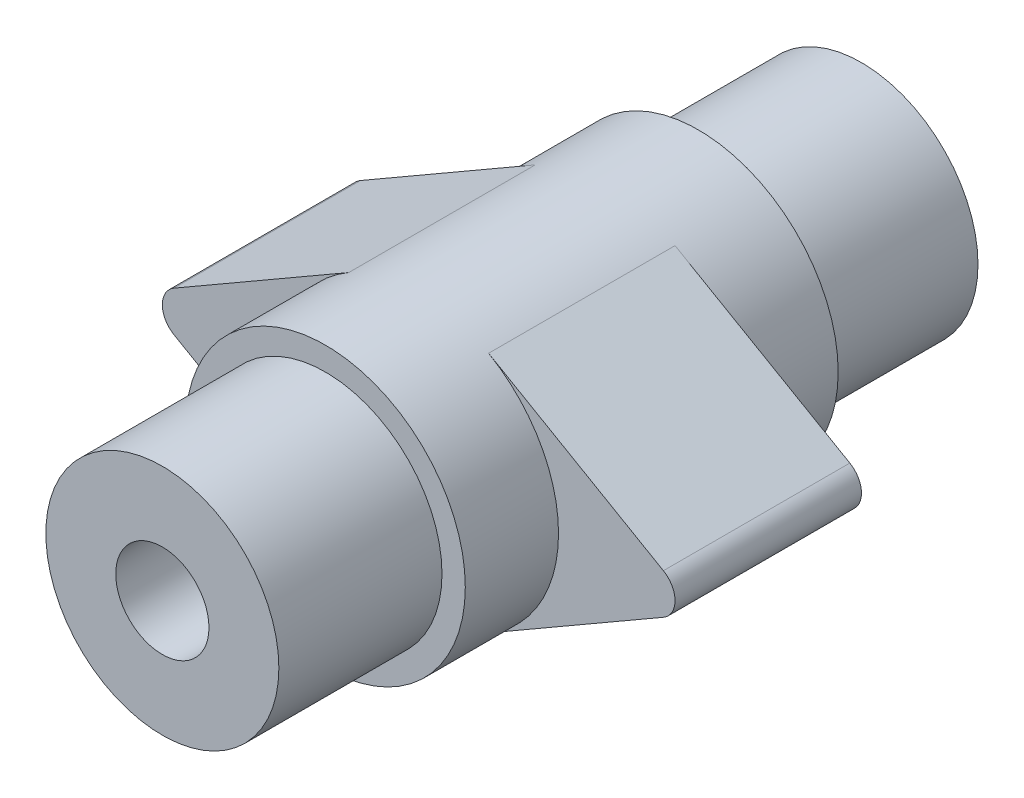
SolidWorks part; units mm, degrees
ref_plane "前视基准面" through (0, 0, 0) normal (0, 0, 1) x (1, 0, 0)
ref_plane "上视基准面" through (0, 0, 0) normal (0, 1, 0) x (1, 0, 0)
ref_plane "右视基准面" through (0, 0, 0) normal (1, 0, 0) x (0, 0, -1)
sketch "草图1" plane through (0, 0, 0) normal (0, 0, 1) x (1, 0, 0)
  circle A0 centre (0, 0) radius 6
extrude "凸台-拉伸1" add sketch "草图1" along normal blind 16 contours A0
sketch "草图3" plane through (0, 0, 0) normal (0, 0, -1) x (-1, 0, 0)
  circle A0 centre (0, 0) radius 5
sketch "草图5" plane through (0, 0, 16) normal (0, 0, 1) x (1, 0, 0)
  circle A0 centre (0, 0) radius 5
sketch "草图8" plane through (0, 0, 0) normal (0, 0, 1) x (1, 0, 0)
  line L10 (3, 5.1962) -> (10.5, 0.866)
  line L11 (-3, -5.1962) -> (-10.5, -0.866)
  line L12 (3, -5.1962) -> (10.5, -0.866)
  line L13 (-3, 5.1962) -> (-10.5, 0.866)
  circle A4 centre (0, 0) radius 6 construction
  arc A5 (3, 5.1962) -> (3, -5.1962) centre (0, 0) cw
  arc A6 (-10.5, 0.866) -> (-10.5, -0.866) centre (-10, 0) ccw
  arc A7 (10.5, 0.866) -> (10.5, -0.866) centre (10, 0) cw
  arc A8 (-3, 5.1962) -> (-3, -5.1962) centre (0, 0) ccw
extrude "凸台-拉伸6" add sketch "草图8" along normal blind 8 from offset 4 contours A7 L10 A5 L12 | A6 L11 A8 L13 region at (7.4822, 0, 0)
sketch "草图9" plane through (0, 0, 16) normal (0, 0, 1) x (1, 0, 0)
  circle A0 centre (0, 0) radius 5
  dimension "D1" = 10
extrude "凸台-拉伸7" add sketch "草图9" along normal blind 7
extrude "凸台-拉伸8" add sketch "草图9<2>" against normal blind 7 from surface starting at face at (6, 0, 0)
sketch "草图9<2>" plane through (0, 0, 16) normal (0, 0, 1) x (1, 0, 0) same geometry as "草图9"
sketch "草图11" plane through (0, 0, 23) normal (0, 0, 1) x (1, 0, 0)
  circle A0 centre (0, 0) radius 2
  dimension "D1" = 4
extrude "切除-拉伸1" cut sketch "草图11" against normal through all
